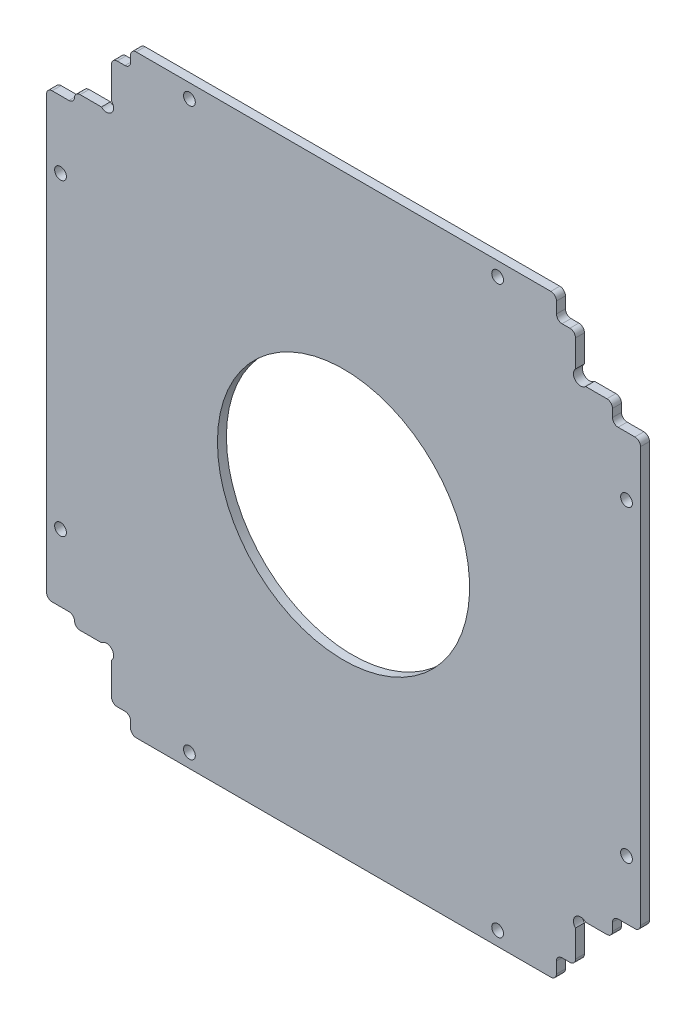
SolidWorks part; units mm, degrees
material "FR4_stuffedProtoboard"
ref_plane "Front Plane" through (0, 0, 0) normal (0, 0, 1) x (1, 0, 0)
ref_plane "Top Plane" through (0, 0, 0) normal (0, 1, 0) x (1, 0, 0)
ref_plane "Right Plane" through (0, 0, 0) normal (1, 0, 0) x (0, 0, -1)
sketch "Sketch1" plane through (0, 0, 0) normal (0, 0, 1) x (1, 0, 0)
  line L0 (53, 53) -> (-53, -53) construction
  line L1 (53, 53) -> (-53, 53)
  line L2 (53, 53) -> (53, -53)
  line L3 (53, -53) -> (-53, -53)
  line L4 (-53, 53) -> (-53, -53)
  point P4 (0, 0)
  dimension "D1" = 106
  dimension "D2" = 106
extrude "mainOutline" add sketch "Sketch1" along normal blind 1.6
sketch "axisLabels" plane through (0, 0, 0) normal (0, 0, -1) x (-1, 0, 0)
  text T0 "+Y"
  text T1 "+X"
sketch "Sketch4" plane through (0, 0, 0) normal (0, 0, -1) x (-1, 0, 0)
  line L1 (-41.4, -41.4) -> (-48, -41.4)
  line L3 (-41.4, -49) -> (-41.4, -41.4)
  line L5 (-60.1065, -39) -> (-49.9975, -39)
  line L7 (-39, -61.4521) -> (-39, -49.9)
  line L9 (39, -56.2753) -> (39, -49.9)
  line L10 (-53, 53) -> (53, 53) construction
  line L11 (41.4, -49.9) -> (41.4, -41.4)
  line L12 (-53, -53) -> (-53, 53) construction
  line L13 (41.4, -41.4) -> (48, -41.4)
  line L15 (48, -40.5) -> (55.5177, -40.5)
  line L17 (55.3838, 40.5) -> (48, 40.5)
  line L19 (39, 57.6877) -> (39, 49.9)
  line L21 (-39, 59.8804) -> (-39, 49.9)
  line L23 (-56.8428, 39) -> (-49.9975, 39)
  line L25 (-41.4, 41.4) -> (-41.4, 49)
  line L27 (-48, 41.4) -> (-41.4, 41.4)
  line L29 (41.4, 49.9) -> (41.4, 41.4)
  line L31 (48, 41.4) -> (41.4, 41.4)
  line L32 (-48, 41.4) -> (-48, 39)
  line L33 (-48, 39) -> (-49.9975, 39)
  line L34 (-41.4, 49) -> (-39, 49)
  line L35 (-39, 49) -> (-39, 49.9)
  line L36 (48, 40.5) -> (48, 41.4)
  line L37 (39, 49.9) -> (41.4, 49.9)
  line L38 (48, -40.5) -> (48, -41.4)
  line L39 (39, -49.9) -> (41.4, -49.9)
  line L40 (-41.4, -49) -> (-39, -49)
  line L41 (-39, -49) -> (-39, -49.9)
  line L42 (-49.9975, -39) -> (-48, -39)
  line L43 (-48, -39) -> (-48, -41.4)
  line L44 (-39, 59.8804) -> (-56.8428, 59.8804)
  line L45 (-56.8428, 59.8804) -> (-56.8428, 39)
  line L46 (53, 53) -> (53, -53) construction
  line L47 (-60.1065, -39) -> (-60.1065, -61.4521)
  line L48 (-60.1065, -61.4521) -> (-39, -61.4521)
  line L49 (39, -56.2753) -> (55.5177, -56.2753)
  line L50 (55.5177, -56.2753) -> (55.5177, -40.5)
  line L51 (55.3838, 40.5) -> (55.3838, 57.6877)
  line L52 (55.3838, 57.6877) -> (39, 57.6877)
  line L53 (53, -53) -> (-53, -53) construction
  dimension "D1" = 14
  dimension "D2" = 11.6
  dimension "D3" = 5
  dimension "D4" = 12.5
  dimension "D5" = 11.6
  dimension "D6" = 3.1
  dimension "D7" = 12.5
  dimension "D8" = 14
  dimension "D9" = 3.1
  dimension "D10" = 5
  dimension "D11" = 11.6
  dimension "D12" = 11.6
  dimension "D13" = 14
  dimension "D14" = 14
  dimension "D15" = 11.6
  dimension "D16" = 11.6
  dimension "D17" = 5
  dimension "D18" = 4
  dimension "D19" = 14
  dimension "D20" = 14
  dimension "D21" = 11.6
  dimension "D22" = 11.6
  dimension "D23" = 4
  dimension "D24" = 5
extrude "railCutouts" cut sketch "Sketch4" against normal through all
sketch "Sketch5" plane through (0, 0, 0) normal (0, 0, -1) x (-1, 0, 0)
  line L0 (-48.898, -39.898) -> (-52.4015, -43.4015) construction
  line L1 (-48, -40.7961) -> (-51.5035, -44.2995) construction
  line L2 (-49.7961, -39) -> (-53.2995, -42.5035) construction
  line L3 (-48, -41.4) -> (-48, -39) construction
  line L4 (-48, 39) -> (-48, 41.4) construction
  line L5 (-42.298, -42.298) -> (-45.4445, -45.4445) construction
  line L6 (-41.4, -43.1961) -> (-44.5465, -46.3425)
  line L7 (-43.1961, -41.4) -> (-46.3425, -44.5465)
  line L8 (-39.898, -49.898) -> (-42.6199, -52.6199) construction
  line L9 (-39, -50.7961) -> (-41.7219, -53.5179) construction
  line L10 (-40.7961, -49) -> (-43.5179, -51.7219) construction
  line L11 (39.898, -50.798) -> (41.4231, -52.3231) construction
  line L12 (40.7961, -49.9) -> (42.3212, -51.4251) construction
  line L13 (39, -51.6961) -> (40.5251, -53.2212) construction
  line L14 (42.298, -42.298) -> (44.0402, -44.0402) construction
  line L15 (43.1961, -41.4) -> (44.9382, -43.1422)
  line L16 (41.4, -43.1961) -> (43.1422, -44.9382)
  line L17 (48.898, -41.398) -> (49.9793, -42.4793) construction
  line L18 (49.7961, -40.5) -> (50.8774, -41.5813) construction
  line L19 (48, -42.2961) -> (49.0813, -43.3774) construction
  line L20 (48.898, 41.398) -> (50.5001, 43.0001) construction
  line L21 (48, 42.2961) -> (49.602, 43.8981) construction
  line L22 (49.7961, 40.5) -> (51.3981, 42.102) construction
  line L23 (42.298, 42.298) -> (44.029, 44.029) construction
  line L24 (41.4, 43.1961) -> (43.131, 44.927)
  line L25 (43.1961, 41.4) -> (44.927, 43.131)
  line L26 (39.898, 50.798) -> (41.2638, 52.1638) construction
  line L27 (39, 51.6961) -> (40.3658, 53.0618) construction
  line L28 (40.7961, 49.9) -> (42.1618, 51.2658) construction
  line L29 (-48.898, 39.898) -> (-50.0606, 41.0606) construction
  line L30 (-49.7961, 39) -> (-50.9587, 40.1626) construction
  line L31 (-48, 40.7961) -> (-49.1626, 41.9587) construction
  line L32 (-42.298, 42.298) -> (-43.7968, 43.7968) construction
  line L33 (-43.1961, 41.4) -> (-44.6948, 42.8988)
  line L34 (-41.4, 43.1961) -> (-42.8988, 44.6948)
  line L35 (-39.898, 49.898) -> (-41.256, 51.256) construction
  line L36 (-40.7961, 49) -> (-42.154, 50.358) construction
  line L37 (-39, 50.7961) -> (-40.358, 52.154) construction
  line L38 (-41.4, 41.4) -> (-41.4, 49) construction
  line L39 (-39, 49) -> (-39, 53) construction
  line L40 (39, 53) -> (39, 49.9) construction
  line L41 (41.4, 49.9) -> (41.4, 41.4) construction
  line L42 (48, 41.4) -> (48, 40.5) construction
  line L43 (39, -49.9) -> (39, -53) construction
  line L44 (41.4, -41.4) -> (41.4, -49.9) construction
  line L45 (53, -40.5) -> (48, -40.5) construction
  line L46 (-39, -53) -> (-39, -49) construction
  line L47 (-41.4, -49) -> (-41.4, -41.4) construction
  arc A0 (-48, -40.7961) -> (-49.7961, -39) centre (-48.898, -39.898) ccw construction
  arc A1 (-53.2995, -42.5035) -> (-51.5035, -44.2995) centre (-52.4015, -43.4015) ccw construction
  arc A2 (-41.4, -43.1961) -> (-43.1961, -41.4) centre (-42.298, -42.298) ccw
  arc A3 (-46.3425, -44.5465) -> (-44.5465, -46.3425) centre (-45.4445, -45.4445) ccw
  arc A4 (-39, -50.7961) -> (-40.7961, -49) centre (-39.898, -49.898) ccw construction
  arc A5 (-43.5179, -51.7219) -> (-41.7219, -53.5179) centre (-42.6199, -52.6199) ccw construction
  arc A6 (40.7961, -49.9) -> (39, -51.6961) centre (39.898, -50.798) ccw construction
  arc A7 (40.5251, -53.2212) -> (42.3212, -51.4251) centre (41.4231, -52.3231) ccw construction
  arc A8 (43.1961, -41.4) -> (41.4, -43.1961) centre (42.298, -42.298) ccw
  arc A9 (43.1422, -44.9382) -> (44.9382, -43.1422) centre (44.0402, -44.0402) ccw
  arc A10 (49.7961, -40.5) -> (48, -42.2961) centre (48.898, -41.398) ccw construction
  arc A11 (49.0813, -43.3774) -> (50.8774, -41.5813) centre (49.9793, -42.4793) ccw construction
  arc A12 (48, 42.2961) -> (49.7961, 40.5) centre (48.898, 41.398) ccw construction
  arc A13 (51.3981, 42.102) -> (49.602, 43.8981) centre (50.5001, 43.0001) ccw construction
  arc A14 (41.4, 43.1961) -> (43.1961, 41.4) centre (42.298, 42.298) ccw
  arc A15 (44.927, 43.131) -> (43.131, 44.927) centre (44.029, 44.029) ccw
  arc A16 (39, 51.6961) -> (40.7961, 49.9) centre (39.898, 50.798) ccw construction
  arc A17 (42.1618, 51.2658) -> (40.3658, 53.0618) centre (41.2638, 52.1638) ccw construction
  arc A18 (-49.7961, 39) -> (-48, 40.7961) centre (-48.898, 39.898) ccw construction
  arc A19 (-49.1626, 41.9587) -> (-50.9587, 40.1626) centre (-50.0606, 41.0606) ccw construction
  arc A20 (-43.1961, 41.4) -> (-41.4, 43.1961) centre (-42.298, 42.298) ccw
  arc A21 (-42.8988, 44.6948) -> (-44.6948, 42.8988) centre (-43.7968, 43.7968) ccw
  arc A22 (-40.7961, 49) -> (-39, 50.7961) centre (-39.898, 49.898) ccw construction
  arc A23 (-40.358, 52.154) -> (-42.154, 50.358) centre (-41.256, 51.256) ccw construction
  point P2 (-50.6498, -41.6498)
  point P9 (-43.8713, -43.8713)
  point P17 (-41.259, -51.259)
  point P24 (40.6606, -51.5606)
  point P31 (43.1691, -43.1691)
  point P38 (49.4387, -41.9387)
  point P45 (49.699, 42.199)
  point P52 (43.1635, 43.1635)
  point P59 (40.5809, 51.4809)
  point P66 (-49.4793, 40.4793)
  point P73 (-43.0474, 43.0474)
  point P80 (-40.577, 50.577)
  dimension "D14" = 1.27
  dimension "D1" = 45
  dimension "D3" = 45
  dimension "D4" = 45
  dimension "D5" = 45
  dimension "D6" = 45
  dimension "D7" = 45
  dimension "D8" = 45
  dimension "D9" = 45
  dimension "D10" = 45
  dimension "D11" = 45
  dimension "D12" = 45
  dimension "D13" = 45
extrude "dogbones" cut sketch "Sketch5" against normal through all
sketch "Sketch6" plane through (0, 0, 0) normal (0, 0, -1) x (-1, 0, 0)
  line L0 (-39, 50) -> (-39, 53) construction
  line L1 (-39, 49) -> (-39, 53) construction
  line L2 (-39, 53) -> (39, 53) construction
  line L3 (-40, 50) -> (-40, 53)
  line L4 (-38, 50) -> (-38, 53)
  line L5 (-49, 39) -> (-53, 39) construction
  line L6 (-53, 39) -> (-48, 39) construction
  line L7 (-49, 38) -> (-53, 38)
  line L8 (-49, 40) -> (-53, 40)
  line L9 (-49, -39) -> (-55.2142, -39) construction
  line L10 (-48, -39) -> (-53, -39) construction
  line L11 (-49, -40) -> (-55.2142, -40)
  line L12 (-49, -38) -> (-55.2142, -38)
  line L13 (-39, -50) -> (-39, -53.9161) construction
  line L14 (-39, -53) -> (-39, -49) construction
  line L15 (-38, -50) -> (-38, -53.9161)
  line L16 (-40, -50) -> (-40, -53.9161)
  line L17 (39, -50.9) -> (39, -54.538) construction
  line L18 (39, -49.9) -> (39, -53) construction
  line L19 (40, -50.9) -> (40, -54.538)
  line L20 (38, -50.9) -> (38, -54.538)
  line L21 (49, -40.5) -> (54.2026, -40.5) construction
  line L22 (53, -40.5) -> (48, -40.5) construction
  line L23 (49, -39.5) -> (54.2026, -39.5)
  line L24 (49, -41.5) -> (54.2026, -41.5)
  line L25 (49, 40.5) -> (54.5566, 40.5) construction
  line L26 (48, 40.5) -> (53, 40.5) construction
  line L27 (49, 41.5) -> (54.5566, 41.5)
  line L28 (49, 39.5) -> (54.5566, 39.5)
  line L29 (39, 50.9) -> (39, 55.8281) construction
  line L30 (39, 53) -> (39, 49.9) construction
  line L31 (38, 50.9) -> (38, 55.8281)
  line L32 (40, 50.9) -> (40, 55.8281)
  line L33 (-48, -41.4) -> (-48, -39) construction
  line L34 (-39, -49) -> (-41.4, -49) construction
  line L35 (41.4, -49.9) -> (39, -49.9) construction
  line L36 (48, -40.5) -> (48, -41.4) construction
  line L37 (48, 41.4) -> (48, 40.5) construction
  line L38 (39, 49.9) -> (41.4, 49.9) construction
  arc A0 (-40, 50) -> (-38, 50) centre (-39, 50) ccw
  arc A1 (-38, 53) -> (-40, 53) centre (-39, 53) ccw
  arc A2 (-49, 38) -> (-49, 40) centre (-49, 39) ccw
  arc A3 (-53, 40) -> (-53, 38) centre (-53, 39) ccw
  arc A4 (-49, -40) -> (-49, -38) centre (-49, -39) ccw
  arc A5 (-55.2142, -38) -> (-55.2142, -40) centre (-55.2142, -39) ccw
  arc A6 (-38, -50) -> (-40, -50) centre (-39, -50) ccw
  arc A7 (-40, -53.9161) -> (-38, -53.9161) centre (-39, -53.9161) ccw
  arc A8 (40, -50.9) -> (38, -50.9) centre (39, -50.9) ccw
  arc A9 (38, -54.538) -> (40, -54.538) centre (39, -54.538) ccw
  arc A10 (49, -39.5) -> (49, -41.5) centre (49, -40.5) ccw
  arc A11 (54.2026, -41.5) -> (54.2026, -39.5) centre (54.2026, -40.5) ccw
  arc A12 (49, 41.5) -> (49, 39.5) centre (49, 40.5) ccw
  arc A13 (54.5566, 39.5) -> (54.5566, 41.5) centre (54.5566, 40.5) ccw
  arc A14 (38, 50.9) -> (40, 50.9) centre (39, 50.9) ccw
  arc A15 (40, 55.8281) -> (38, 55.8281) centre (39, 55.8281) ccw
  point P6 (-39, 51.5)
  point P11 (-51, 39)
  point P21 (-52.1071, -39)
  point P30 (-39, -51.958)
  point P39 (39, -52.719)
  point P48 (51.6013, -40.5)
  point P57 (51.7783, 40.5)
  point P66 (39, 53.364)
  point P75 (-39, 49)
  dimension "D1" = 1
extrude "solarFillets" cut sketch "Sketch6" against normal through all
fillet "handlingFillets" radius 1 16 edges at (-41.4, -49.9, 0.8) (-38, -53, 0.8) (-53, -39.5, 0.8) (-48, -41.4, 0.8) (-48, 41.4, 0.8) (-53, 39.5, 0.8) (-41.4, 49.9, 0.8) (-38, 53, 0.8) (38, 53, 0.8) (41.4, 49, 0.8) (48, 41.4, 0.8) (53, 38, 0.8) (53, -38, 0.8) (48, -41.4, 0.8) (41.4, -49, 0.8) (38, -53, 0.8)
sketch "Sketch7" plane through (0, 0, 1.6) normal (0, 0, 1) x (1, 0, 0)
  line L0 (-37, -53) -> (37, -53) construction
  line L1 (-53, 38.5) -> (-53, -38.5) construction
  line L2 (37, 53) -> (-37, 53) construction
  line L3 (-31.37, 28.67) -> (-31.37, 31.21) construction
  line L4 (-31.37, 31.21) -> (-28.83, 31.21) construction
  line L5 (-28.83, 31.21) -> (-28.83, 28.67) construction
  line L6 (-28.83, 28.67) -> (-31.37, 28.67) construction
  line L7 (-31.37, 28.67) -> (-28.83, 31.21) construction
  circle A1 centre (-28.4723, -17.925) radius 0.8
  circle A3 centre (-28.4723, -33.775) radius 0.8
  circle A5 centre (-31.37, 28.67) radius 0.425
  circle A7 centre (-28.83, 28.67) radius 0.425
  circle A9 centre (-30.1, 29.94) radius 0.425
  circle A10 centre (-28.83, 31.21) radius 0.425
  circle A11 centre (-31.37, 31.21) radius 0.425
  circle A12 centre (-31.37, 21.27) radius 0.425
  circle A13 centre (-28.83, 21.27) radius 0.425
  circle A14 centre (-30.1, 22.54) radius 0.425
  circle A15 centre (-28.83, 23.81) radius 0.425
  circle A16 centre (-31.37, 23.81) radius 0.425
  circle A17 centre (-31.37, 13.87) radius 0.425
  circle A18 centre (-28.83, 13.87) radius 0.425
  circle A19 centre (-30.1, 15.14) radius 0.425
  circle A20 centre (-28.83, 16.41) radius 0.425
  circle A21 centre (-31.37, 16.41) radius 0.425
  point P13 (-30.1, 29.94)
  dimension "D8" = 1.6
  dimension "D9" = 3
  dimension "D6" = 0.85
  dimension "D1" = 19.225
  dimension "D2" = 24.5277
  dimension "D3" = 15.85
  dimension "D4" = 23.06
  dimension "D5" = 22.9
  dimension "D7" = 2.54
  dimension "D10" = 7.4
extrude "connectorHoles" [suppressed] cut sketch "Sketch7" against normal through all
hole_wizard "M2 Clearance Hole1" positions "Sketch8" profile "Sketch9" hole size "M2" standard "ANSI Metric" end condition through all
sketch "Sketch8" plane through (0, 0, 0) normal (0, 0, -1) x (-1, 0, 0)
  line L0 (53, 38.5) -> (53, -38.5) construction
  line L1 (37, -53) -> (-37, -53) construction
  line L2 (-53, -37) -> (-53, 37) construction
  line L3 (53, 0) -> (-53, 0) construction
  line L5 (0, -53) -> (0, -11.6379) construction
  point P0 (50.5, -27.5)
  point P1 (27.5, -50.5)
  point P5 (-50.5, -27.5)
  point P30 (-27.5, -50.5)
  point P31 (-27.5, 50.5)
  point P32 (-50.5, 27.5)
  point P33 (27.5, 50.5)
  point P34 (50.5, 27.5)
  dimension "D1" = 2.5
  dimension "D2" = 2.5
  dimension "D3" = 55
  dimension "D4" = 2.5
  dimension "D5" = 55
  dimension "D6" = 55
sketch "Sketch9" plane through (-50.5, -27.5, 0) normal (1, 0, 0) x (0, 1, 0)
  line L0 (0, 0) -> (0, 1.6)
  line L1 (0, 1.6) -> (1.05, 1.6)
  line L2 (1.05, 1.6) -> (1.05, 0)
  line L5 (1.05, 0) -> (0, 0)
  line L11 (0, -6.35) -> (0, 107.95) construction
  dimension "Thru Hole Dia." = 2.1
  dimension "Thru Hole Depth" = 1.6
sketch "Sketch10" [suppressed] plane through (0, 0, 0) normal (0, 0, -1) x (-1, 0, 0)
  circle A0 centre (0, 0) radius 42.5
  dimension "D1" = 85
extrude "Cut-Extrude1" [suppressed] cut sketch "Sketch10" against normal through all both and the other way through all
sketch "Sketch11" plane through (0, 0, 0) normal (0, 0, -1) x (-1, 0, 0)
  circle A0 centre (0, 0) radius 22.5
  dimension "D1" = 45
extrude "Cut-Extrude2" cut sketch "Sketch11" against normal through all both and the other way through all
